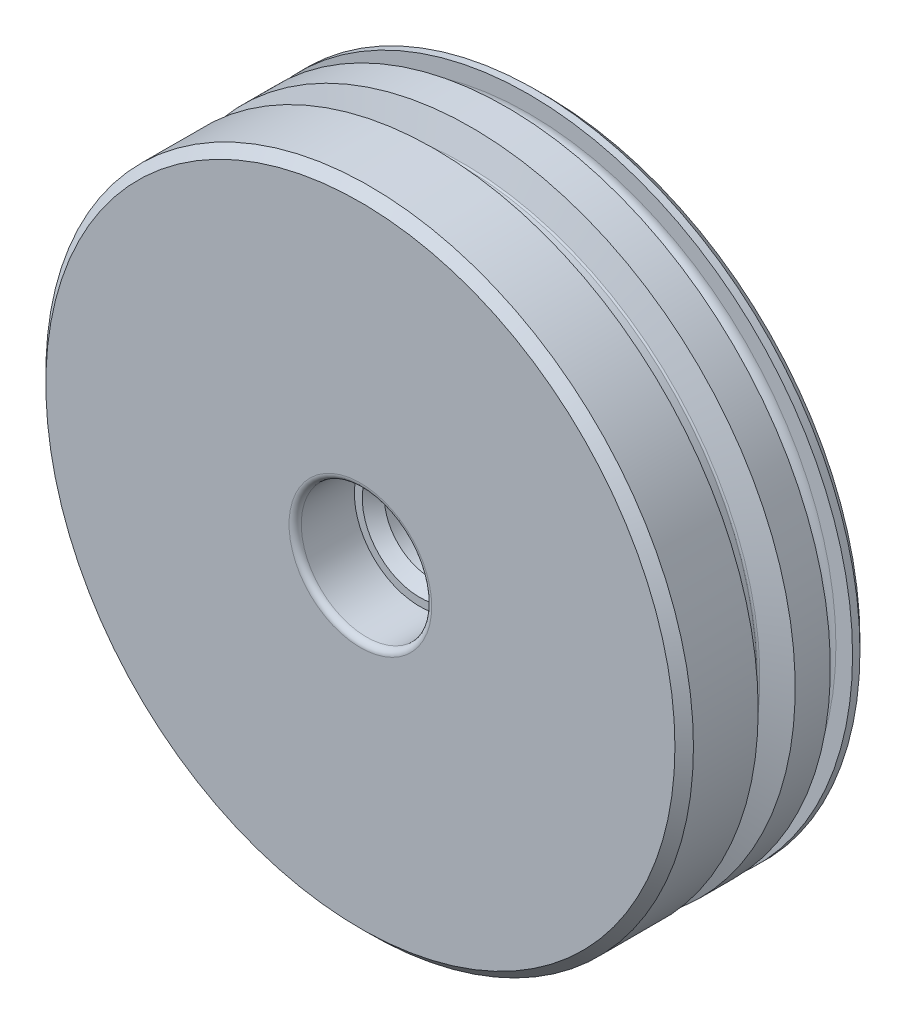
SolidWorks part; units mm, degrees
material "Delrin 2700 NC010, Low Viscosity Acetal Copolymer (SS)"
ref_plane "Front Plane" through (0, 0, 0) normal (0, 0, 1) x (1, 0, 0)
ref_plane "Top Plane" through (0, 0, 0) normal (0, 1, 0) x (1, 0, 0)
ref_plane "Right Plane" through (0, 0, 0) normal (1, 0, 0) x (0, 0, -1)
sketch "Sketch1" plane through (0, 0, 0) normal (0, 0, 1) x (1, 0, 0)
  circle A0 centre (0, 0) radius 17.5
  dimension "D1" = 35
extrude "Boss-Extrude1" add sketch "Sketch1" along normal blind 5 and the other way blind 5
sketch "Sketch3" plane through (0, 0, 0) normal (1, 0, 0) x (0, 0, -1)
  line L0 (0, 19.25) -> (0, -19.25) construction
  line L2 (-1, 17.5) -> (-0.5228, 16.0684)
  line L4 (-0.4279, 16) -> (0.4279, 16)
  line L5 (-1, 17.5) -> (1, 17.5)
  line L6 (0.5228, 16.0684) -> (1, 17.5)
  arc A0 (0.4279, 16) -> (0.5228, 16.0684) centre (0.4279, 16.1) ccw
  arc A1 (-0.4279, 16) -> (-0.5228, 16.0684) centre (-0.4279, 16.1) cw
  point P1 (0, 16)
  point P5 (0, 17.5)
  point P10 (0.5, 16)
  point P14 (-0.5, 16)
  dimension "D1" = 1
  dimension "D4" = 0.1
  dimension "D2" = 2
  dimension "D3" = 1.5
ref_axis "Axis1" through (0, 0, -0.35) along (0, 0, 1)
revolve "Cut-Revolve1" cut sketch "Sketch3" angle 360 about axis through (0, 0, -0.35) along (0, 0, 1)
sketch "Sketch2" plane through (0, 0, 5) normal (0, 0, 1) x (1, 0, 0)
  circle A0 centre (0, 0) radius 3.525
  dimension "D1" = 7.05
extrude "Cut-Extrude1" cut sketch "Sketch2" against normal blind 3.2
chamfer "Chamfer1" distance 0.5 angle 45 2 edges at (17.5, 0, 5) (17.5, 0, -5)
sketch "Sketch4" plane through (0, 0, 1.8) normal (0, 0, 1) x (1, 0, 0)
  circle A0 centre (0, 0) radius 2.5
  dimension "D1" = 5
extrude "Cut-Extrude2" cut sketch "Sketch4" against normal through all
ref_axis "Axis2" through (0, 19.25, 5) along (0, -1, 0)
chamfer "Chamfer2" distance 0.6 angle 45 1 edges at (2.5, 0, 1.8)
mirror "Mirror2" about plane through (0, 0, 0) normal (0, 0, 1) of "Chamfer2", "Cut-Extrude1"
ref_plane "Plane4" through (0, 17.5, 0) normal (0, 1, 0) x (1, 0, 0)
sketch "Sketch7" plane through (0, 0, 0) normal (1, 0, 0) x (0, 0, -1)
  line L5 (4.5, 17.5) -> (4.5, -17.5) construction
  line L7 (2.9, 16.6) -> (2.9, 17.5)
  line L8 (2.9, 17.5) -> (4.1, 17.5)
  line L9 (4.1, 17.5) -> (4.1, 16.6)
  line L10 (3.5, 16) -> (4.2963, 16) construction
  arc A0 (2.9, 16.6) -> (4.1, 16.6) centre (3.5, 16.6) ccw
  dimension "D1" = 1.2
  dimension "D3" = 1.5
  dimension "D2" = 1
revolve "Cut-Revolve3" cut sketch "Sketch7" angle 360 about axis through (0, 0, -0.35) along (0, 0, 1)
fillet "Fillet1" radius 0.33 2 edges at (3.525, 0, 5) (3.525, 0, -5)
sketch "Sketch9" plane through (0, 0, -5) normal (0, 0, -1) x (-1, 0, 0)
  line L0 (-4.45, 1.55) -> (-7.55, 1.55)
  line L1 (7.55, 1.55) -> (4.45, 1.55)
  line L2 (7.55, 1.55) -> (7.55, -1.55)
  line L3 (7.55, -1.55) -> (4.45, -1.55)
  line L4 (4.45, 1.55) -> (4.45, -1.55)
  line L5 (7.55, 1.55) -> (4.45, -1.55) construction
  line L6 (7.55, -1.55) -> (4.45, 1.55) construction
  line L7 (-4.45, 1.55) -> (-4.45, -1.55)
  line L8 (-4.45, -1.55) -> (-7.55, -1.55)
  line L9 (-7.55, 1.55) -> (-7.55, -1.55)
  line L10 (-4.45, 1.55) -> (-7.55, -1.55) construction
  line L11 (-4.45, -1.55) -> (-7.55, 1.55) construction
  line L13 (0, 0) -> (4.45, 0) construction
  line L14 (0, 0) -> (-4.45, 0) construction
  point P0 (6, 0)
  point P5 (-6, 0)
  dimension "D1" = 3.1
  dimension "D2" = 3.1
  dimension "D3" = 3.1
  dimension "D4" = 3.1
  dimension "D5" = 12
extrude "Cut-Extrude4" cut sketch "Sketch9" against normal blind 4
